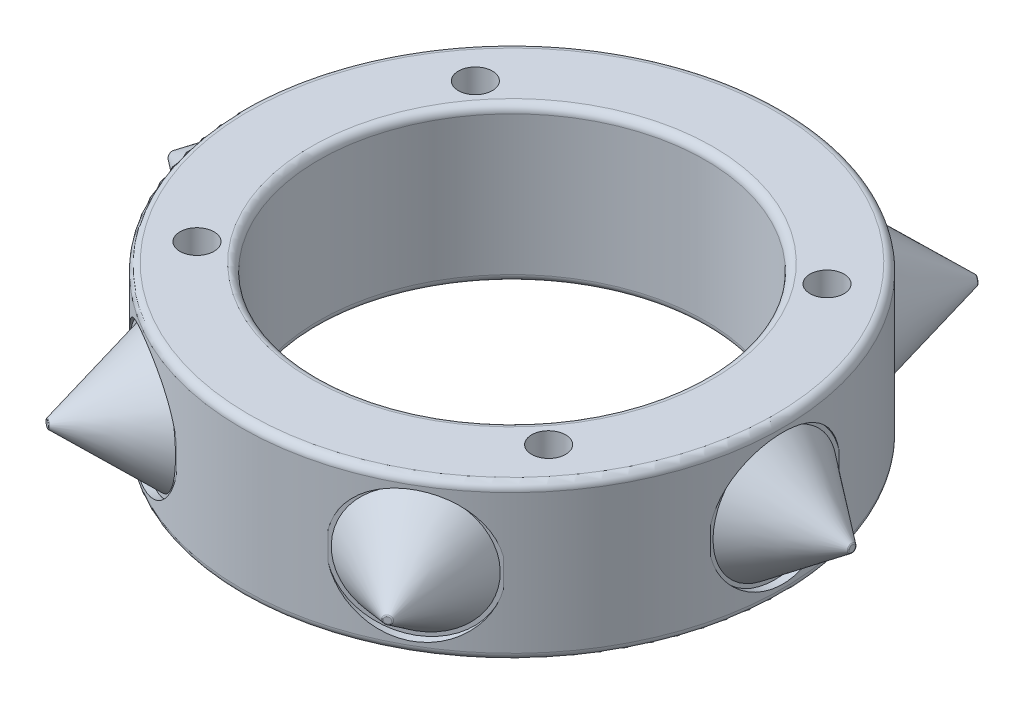
SolidWorks part; units mm, degrees
material "ABS"
ref_plane "正面" through (0, 0, 0) normal (0, 0, 1) x (1, 0, 0)
ref_plane "平面" through (0, 0, 0) normal (0, 1, 0) x (1, 0, 0)
ref_plane "右側面" through (0, 0, 0) normal (1, 0, 0) x (0, 0, -1)
sketch "ｽｹｯﾁ1" plane through (0, 0, 0) normal (0, 1, 0) x (1, 0, 0)
  circle A0 centre (0, 0) radius 17.5
  circle A1 centre (0, 0) radius 12.5
  dimension "D1" = 25
  dimension "D2" = 35
extrude "ﾎﾞｽ - 押し出し1" add sketch "ｽｹｯﾁ1" along normal blind 5 and the other way blind 5
fillet "ﾌｨﾚｯﾄ1" radius 0.5 4 edges at (0, -5, 12.5) (0, -5, 17.5) (0, 5, 12.5) (0, 5, 17.5)
sketch "ｽｹｯﾁ2" plane through (0, 0, 0) normal (0, 0, 1) x (1, 0, 0)
  line L0 (21.96, 0.28) -> (17, 4)
  line L1 (17, 4) -> (17, 0)
  line L2 (17, 0) -> (22, 0) construction
  line L4 (-17.5, 4.5) -> (17.5, 4.5) construction
  line L5 (-17.5, 4.5) -> (17.5, 4.5) construction
  line L6 (22, 0) -> (17, 0)
  line L7 (22, 0) -> (22, 0.2)
  arc A0 (22, 0.2) -> (21.96, 0.28) centre (21.9, 0.2) ccw
  point P4 (22, 0.25)
  dimension "D5" = 0.1
  dimension "D1" = 0.5
  dimension "D2" = 4
  dimension "D3" = 5
  dimension "D4" = 0.25
revolve "回転1" add sketch "ｽｹｯﾁ2" angle 360 about L6 region at (18.7646, 1.3383, 0)
ref_axis "軸1" through (0, -4.5, 0) along (0, 1, 0)
pattern_circular "円形ﾊﾟﾀｰﾝ5" count 6 over 360 about axis through (0, -4.5, 0) along (0, 1, 0) of bodies 102
sketch "ｽｹｯﾁ3" plane through (-8.5, 0, 14.7224) normal (0.5, 0, -0.866) x (-0.866, 0, -0.5)
  circle A0 centre (0, 0) radius 4.25
  dimension "D1" = 8.5
extrude "ｶｯﾄ - 押し出し1" cut sketch "ｽｹｯﾁ3" against normal blind 10
pattern_circular "円形ﾊﾟﾀｰﾝ6" count 6 over 360 about axis through (0, -4.5, 0) along (0, 1, 0) of "ｶｯﾄ - 押し出し1"
sketch "ｽｹｯﾁ4" plane through (0, 5, 0) normal (0, 1, 0) x (1, 0, 0)
  line L0 (0, 0) -> (34.9885, 0) construction
  line L1 (0, 0) -> (0, 31.4093) construction
  circle A0 centre (0, 0) radius 14.5 construction
  circle A1 centre (11.3688, 9) radius 1.1
  circle A2 centre (11.3688, -9) radius 1.1
  circle A3 centre (-11.3688, -9) radius 1.1
  circle A4 centre (-11.3688, 9) radius 1.1
  dimension "D1" = 29
  dimension "D2" = 2.2
  dimension "D3" = 9
extrude "ｶｯﾄ - 押し出し2" cut sketch "ｽｹｯﾁ4" against normal through all
